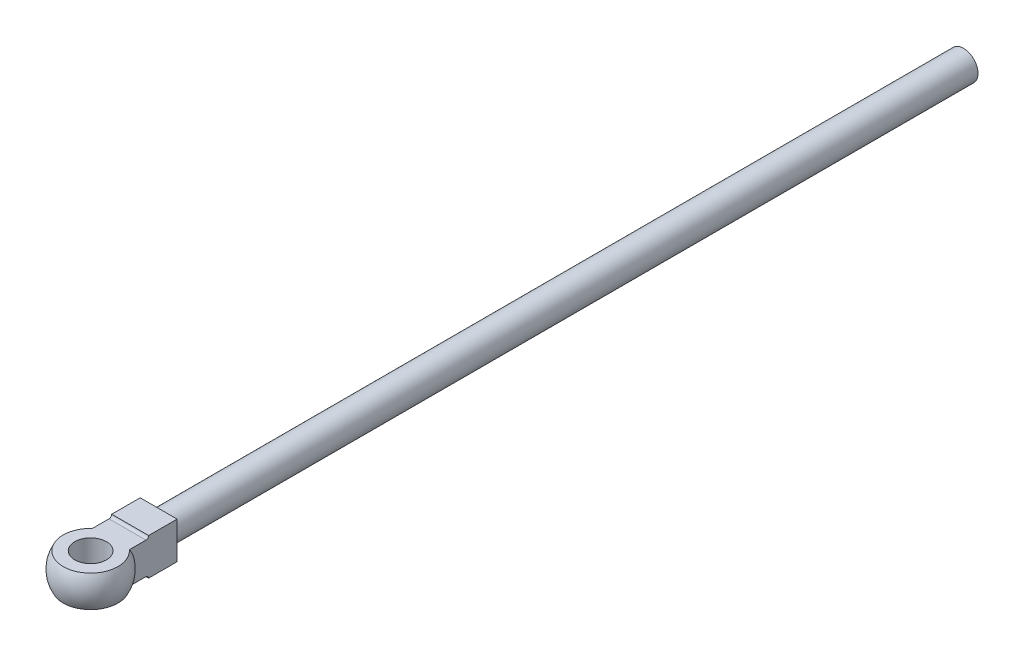
SolidWorks part; units mm, degrees
material "45"
ref_plane "前视基准面" through (0, 0, 0) normal (0, 0, 1) x (1, 0, 0)
ref_plane "上视基准面" through (0, 0, 0) normal (0, 1, 0) x (1, 0, 0)
ref_plane "右视基准面" through (0, 0, 0) normal (1, 0, 0) x (0, 0, -1)
sketch "草图3" plane through (0, 0, 0) normal (0, 0, 1) x (1, 0, 0)
  line L0 (0, 0) -> (-30, 0) construction
  line L1 (-30, -30) -> (-30, 30)
  line L2 (-30, 30) -> (-51.9615, 30)
  line L3 (-30, -30) -> (-51.9615, -30)
  line L4 (0, 0) -> (0, 23.2747) construction
  arc A0 (-51.9615, 30) -> (-51.9615, -30) centre (0, 0) ccw
  point P5 (-30, 0)
  dimension "D3" = 120
  dimension "D1" = 30
  dimension "D2" = 60
revolve "旋转1" add sketch "草图3" angle 360 about L4
ref_plane "基准面1" through (0, 0, -130) normal (0, 0, 1) x (1, 0, 0)
sketch "草图5" plane through (0, 0, -130) normal (0, 0, 1) x (1, 0, 0)
  line L1 (-35, -35) -> (35, -35)
  line L2 (-35, -35) -> (-35, 35)
  line L3 (-35, 35) -> (35, 35)
  line L4 (35, -35) -> (35, 35)
  line L5 (-35, -35) -> (35, 35) construction
  line L6 (-35, 35) -> (35, -35) construction
  point P0 (0, 0)
  dimension "D1" = 70
  dimension "D2" = 70
extrude "凸台-拉伸2" add sketch "草图5" along normal blind 130
sketch "草图11" plane through (0, 0, -130) normal (0, 0, -1) x (-1, 0, 0)
  circle A0 centre (0, 0) radius 27.5
  dimension "D1" = 55
extrude "凸台-拉伸4" add sketch "草图11" along normal blind 1525
sketch "草图12" plane through (0, 0, 0) normal (0, 0, 1) x (1, 0, 0)
  line L0 (51.9615, 30) -> (-51.9615, 30) construction
  line L1 (51.9615, 30) -> (-51.9615, 30)
  line L2 (-51.9615, -30) -> (51.9615, -30) construction
  line L3 (-51.9615, -30) -> (51.9615, -30)
  line L4 (-51.9615, 30) -> (-51.9615, 38.0948)
  line L5 (-51.9615, 38.0948) -> (51.9615, 38.0948)
  line L6 (51.9615, 38.0948) -> (51.9615, 30)
  line L7 (51.9615, -30) -> (51.9615, -40.3677)
  line L8 (51.9615, -40.3677) -> (-51.9615, -40.3677)
  line L9 (-51.9615, -30) -> (-51.9615, -40.3677)
extrude "切除-拉伸1" cut sketch "草图12" against normal blind 75
sketch "草图13" plane through (0, -30, 0) normal (0, -1, 0) x (1, 0, 0)
  circle A0 centre (0, 0) radius 30
extrude "切除-拉伸2" cut sketch "草图13" against normal blind 75
fillet "圆角3" radius 5 2 edges at (0, -30, -75) (0, 30, -75)
fillet "圆角2" radius 1 1 edges at (-27.5, 0, -130)
chamfer "倒角2" distance 1 angle 45 4 edges at (0, 35, -130) (0, -35, -130) (-35, 0, -130) (35, 0, -130)
